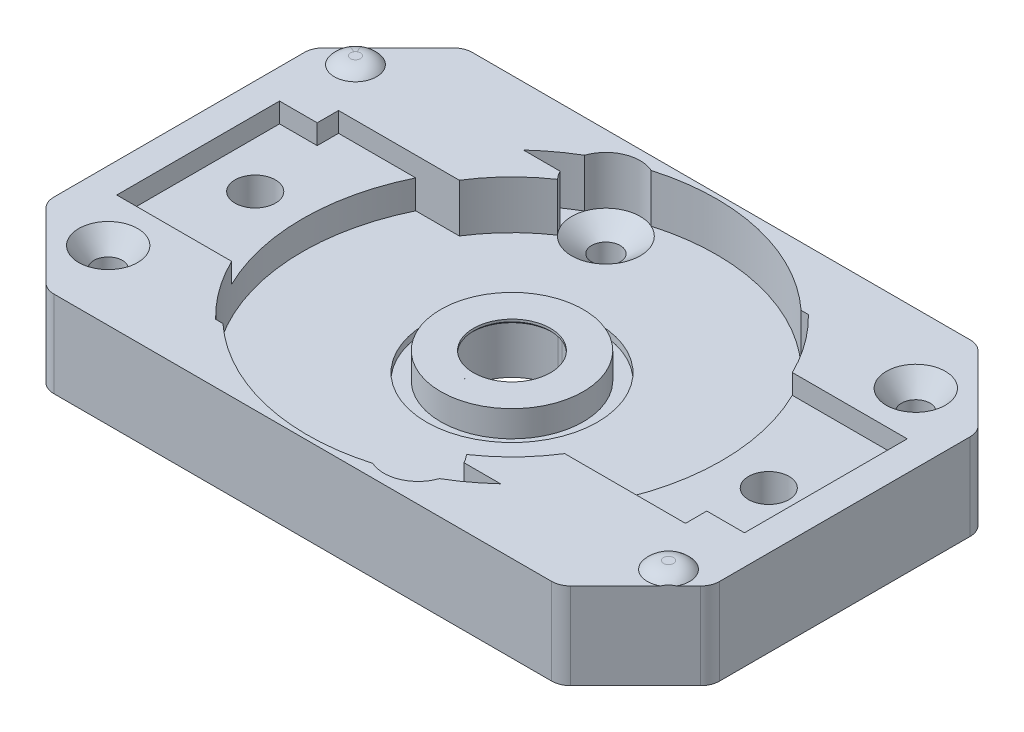
SolidWorks part; units mm, degrees
ref_plane "Front Plane" through (0, 0, 0) normal (0, 0, 1) x (1, 0, 0)
ref_plane "Top Plane" through (0, 0, 0) normal (0, 1, 0) x (1, 0, 0)
ref_plane "Right Plane" through (0, 0, 0) normal (1, 0, 0) x (0, 0, -1)
sketch "Sketch3" plane through (0, 0, 0) normal (0, 1, 0) x (-1, 0, 0)
  line L53 (-27.5858, 21.4142) -> (-34.4142, 14.5858)
  line L55 (-35, 13.1716) -> (-35, -13.1716)
  line L56 (-34.4142, -14.5858) -> (-27.5858, -21.4142)
  line L57 (-26.1716, -22) -> (26.1716, -22)
  line L58 (27.5858, -21.4142) -> (34.4142, -14.5858)
  line L59 (35, -13.1716) -> (35, 13.1716)
  line L60 (34.4142, 14.5858) -> (27.5858, 21.4142)
  line L61 (26.1716, 22) -> (-26.1716, 22)
  line L62 (21.5631, 19) -> (-21.5631, 19)
  line L63 (32, 12.7574) -> (28.5281, 16.2292)
  line L64 (32, -12.7574) -> (32, 12.7574)
  line L65 (28.5281, -16.2292) -> (32, -12.7574)
  line L67 (-21.5631, -19) -> (21.5631, -19)
  line L68 (-32, -12.7574) -> (-28.5281, -16.2292)
  line L69 (-32, 12.7574) -> (-32, -12.7574)
  line L70 (-28.5281, 16.2292) -> (-32, 12.7574)
  line L71 (0, 22) -> (0, -22) construction
  line L73 (-35, 0) -> (35, 0) construction
  circle A2 centre (0, -3.937) radius 1.125
  circle A4 centre (0, 3.937) radius 1.125
  circle A6 centre (25, -17.5) radius 1.5
  arc A7 (-34.4142, 14.5858) -> (-35, 13.1716) centre (-33, 13.1716) ccw
  circle A8 centre (0, 0) radius 7.493
  arc A10 (-35, -13.1716) -> (-34.4142, -14.5858) centre (-33, -13.1716) ccw
  circle A18 centre (0, 0) radius 1.125
  arc A19 (-27.5858, -21.4142) -> (-26.1716, -22) centre (-26.1716, -20) ccw
  arc A47 (26.1716, -22) -> (27.5858, -21.4142) centre (26.1716, -20) ccw
  arc A48 (34.4142, -14.5858) -> (35, -13.1716) centre (33, -13.1716) ccw
  arc A49 (35, 13.1716) -> (34.4142, 14.5858) centre (33, 13.1716) ccw
  arc A50 (27.5858, 21.4142) -> (26.1716, 22) centre (26.1716, 20) ccw
  arc A51 (-26.1716, 22) -> (-27.5858, 21.4142) centre (-26.1716, 20) ccw
  arc A52 (-28.5281, 16.2292) -> (-21.5631, 19) centre (-25, 17.5) ccw
  arc A53 (21.5631, 19) -> (28.5281, 16.2292) centre (25, 17.5) ccw
  arc A54 (28.5281, -16.2292) -> (21.5631, -19) centre (25, -17.5) ccw
  arc A55 (-21.5631, -19) -> (-28.5281, -16.2292) centre (-25, -17.5) ccw
  circle A56 centre (25, 17.5) radius 1.5
  circle A57 centre (-25, 17.5) radius 1.5
  circle A58 centre (-25, -17.5) radius 1.5
  point P0 (0, 0)
  dimension "D1" = 14.986
  dimension "D2" = 2.25
  dimension "D5" = 3
  dimension "D3" = 7.874
extrude "Boss-Extrude1" add sketch "Sketch3" along normal blind 4 contours A8 | A8 A18 A2 A4 | L61 A51 L53 A7 L55 A10 L56 A19 L57 A47 L58 A48 L59 A49 L60 A50 A58 A57 A56 A6 L67 A55 L68 L69 L70 A52 L62 A53 L63 L64 L65 A54 | A58 | A6 | A56 | A57 region at (26.6205, 0, 21.0839) region at (-23.3387, 0, 13.324) region at (-25, 0, -17.5) region at (7.2811, 0, 0) region at (-25, 0, 17.5) region at (25, 0, 17.5) region at (25, 0, -17.5)
sketch "Sketch2" plane through (0, 4, 0) normal (0, 1, 0) x (1, 0, 0)
  line L0 (8.6989, -15.799) -> (22.987, -15.799)
  line L2 (-27.9195, 7.436) -> (-27.9195, 9.678)
  line L3 (-27.9195, 9.678) -> (-15.2189, 9.678)
  line L4 (27.9195, -9.678) -> (27.9195, -7.436)
  line L5 (15.2189, -9.678) -> (27.9195, -9.678)
  line L7 (-22.987, -15.799) -> (-15.3666, -15.799)
  line L9 (-22.987, 15.799) -> (-8.6989, 15.799)
  line L11 (15.3666, 15.799) -> (22.987, 15.799)
  line L12 (-31.8805, -9.678) -> (-19.8009, -9.678)
  line L13 (-31.8805, -9.678) -> (-31.8805, 7.436)
  line L14 (-31.8805, 7.436) -> (-27.9195, 7.436)
  line L15 (31.8805, 9.678) -> (19.8009, 9.678)
  line L16 (31.8805, 9.678) -> (31.8805, -7.436)
  line L17 (31.8805, -7.436) -> (27.9195, -7.436)
  line L19 (-22.987, -15.799) -> (-22.987, -22)
  line L21 (22.987, -15.799) -> (22.987, -22)
  line L25 (-31.8805, 0) -> (31.8805, 0) construction
  line L26 (22.987, 15.799) -> (22.987, 22)
  line L28 (-22.987, 15.799) -> (-22.987, 22)
  line L33 (-26.1716, -22) -> (26.1716, -22)
  line L34 (27.5858, -21.4142) -> (34.4142, -14.5858)
  line L35 (35, -13.1716) -> (35, 13.1716)
  line L36 (34.4142, 14.5858) -> (27.5858, 21.4142)
  line L37 (26.1716, 22) -> (-26.1716, 22)
  line L38 (-27.5858, 21.4142) -> (-34.4142, 14.5858)
  line L40 (-35, 13.1716) -> (-35, -13.1716)
  line L41 (-34.4142, -14.5858) -> (-27.5858, -21.4142)
  line L42 (-26.1716, -22) -> (26.1716, -22)
  line L43 (27.5858, -21.4142) -> (34.4142, -14.5858)
  line L44 (35, -13.1716) -> (35, 13.1716)
  line L46 (34.4142, 14.5858) -> (27.5858, 21.4142)
  line L48 (26.1716, 22) -> (-26.1716, 22)
  line L49 (-27.5858, 21.4142) -> (-34.4142, 14.5858)
  line L51 (-35, 13.1716) -> (-35, -13.1716)
  line L53 (-34.4142, -14.5858) -> (-27.5858, -21.4142)
  arc A0 (-19.8009, -9.678) -> (-15.3666, -15.799) centre (0, 0) ccw
  arc A1 (8.6989, -15.799) -> (15.2189, -9.678) centre (0, 0) ccw
  arc A2 (-8.6989, 15.799) -> (-15.2189, 9.678) centre (0, 0) ccw
  arc A3 (19.8009, 9.678) -> (15.3666, 15.799) centre (0, 0) ccw
  circle A4 centre (-27, 0) radius 2.125
  circle A5 centre (27, 0) radius 2.125
  arc A6 (-19.8009, -9.678) -> (-19.8009, 9.678) centre (0, 0) cw
  arc A7 (19.8009, 9.678) -> (19.8009, -9.678) centre (0, 0) cw
  arc A22 (26.1716, -22) -> (27.5858, -21.4142) centre (26.1716, -20) ccw
  arc A24 (34.4142, -14.5858) -> (35, -13.1716) centre (33, -13.1716) ccw
  arc A25 (35, 13.1716) -> (34.4142, 14.5858) centre (33, 13.1716) ccw
  arc A27 (27.5858, 21.4142) -> (26.1716, 22) centre (26.1716, 20) ccw
  arc A28 (-26.1716, 22) -> (-27.5858, 21.4142) centre (-26.1716, 20) ccw
  arc A42 (-34.4142, 14.5858) -> (-35, 13.1716) centre (-33, 13.1716) ccw
  arc A43 (-35, -13.1716) -> (-34.4142, -14.5858) centre (-33, -13.1716) ccw
  arc A56 (-27.5858, -21.4142) -> (-26.1716, -22) centre (-26.1716, -20) ccw
  arc A57 (26.1716, -22) -> (27.5858, -21.4142) centre (26.1716, -20) ccw
  arc A58 (34.4142, -14.5858) -> (35, -13.1716) centre (33, -13.1716) ccw
  arc A59 (35, 13.1716) -> (34.4142, 14.5858) centre (33, 13.1716) ccw
  arc A60 (27.5858, 21.4142) -> (26.1716, 22) centre (26.1716, 20) ccw
  arc A61 (-26.1716, 22) -> (-27.5858, 21.4142) centre (-26.1716, 20) ccw
  arc A62 (-34.4142, 14.5858) -> (-35, 13.1716) centre (-33, 13.1716) ccw
  arc A63 (-35, -13.1716) -> (-34.4142, -14.5858) centre (-33, -13.1716) ccw
  arc A64 (-27.5858, -21.4142) -> (-26.1716, -22) centre (-26.1716, -20) ccw
  dimension "D1" = 36.071
  dimension "D2" = 44.079
  dimension "D8" = 4.25
  dimension "D3" = 55.839
  dimension "D4" = 63.761
  dimension "D5" = 19.356
  dimension "D6" = 31.598
  dimension "D7" = 54
  dimension "D9" = 2.242
  dimension "D10" = 2.242
  dimension "D11" = 0
extrude "Boss-Extrude2" add sketch "Sketch2" along normal blind 3 contours L15 A7 L5 L4 L17 L16 A5 | L12 A6 L3 L2 L14 L13 A4 | L25 L13 L12 A6 A4 | A7 L25 A5 L16 L15 region at (26.197, 4, 4.9802) region at (26.5424, 4, -5.3138) region at (-26.5424, 4, 5.3138) region at (-26.197, 4, -4.9802)
extrude "Boss-Extrude3" add sketch "Sketch2<4>" along normal blind 5.08 contours A3 L15 L16 L17 L4 L5 A1 L0 L11 | A2 L9 L7 A0 L12 L13 L14 L2 L3 region at (12.6952, 4, 13.5228) region at (-24.5793, 4, 21.4874)
sketch "Sketch2<4>" plane through (0, 4, 0) normal (0, 1, 0) x (1, 0, 0) same geometry as "Sketch2"
sketch "Sketch4" plane through (0, 4, 0) normal (0, 1, 0) x (1, 0, 0)
  circle A0 centre (0, 0) radius 7.493
  circle A1 centre (0, 0) radius 9
  circle A2 centre (0, 3.937) radius 1.125
  circle A3 centre (0, 0) radius 1.125
  circle A4 centre (0, -3.937) radius 1.125
  dimension "D1" = 14.986
  dimension "D2" = 18
extrude "Boss-Extrude4" add sketch "Sketch4" along normal blind 2.02 contours A0 A4 A3 A2 region at (-7.2811, 4, 0)
extrude "Cut-Extrude1" cut sketch "Sketch4<3>" against normal blind 0.728 contours A1 A0 region at (-8.7454, 4, 0)
sketch "Sketch4<3>" plane through (0, 4, 0) normal (0, 1, 0) x (1, 0, 0) same geometry as "Sketch4"
sketch "Sketch7" plane through (0, 7, 0) normal (0, 1, 0) x (1, 0, 0)
  circle A0 centre (-27, 0) radius 2.125
  circle A1 centre (27, 0) radius 2.125
extrude "Cut-Extrude3" cut sketch "Sketch7" against normal through all
sketch "Sketch8" plane through (0, 0, 0) normal (0, -1, 0) x (1, 0, 0)
  circle A0 centre (-27.7296, 14.7296) radius 1.5
  circle A1 centre (7.5, 17.375) radius 1.5
  circle A2 centre (27.7296, -14.7296) radius 1.5
  circle A3 centre (-7.5, -17.375) radius 1.5
  dimension "D1" = 3
extrude "Cut-Extrude4" cut sketch "Sketch8" against normal through all
sketch "Sketch10" plane through (0, 4, 0) normal (0, 1, 0) x (1, 0, 0)
  circle A0 centre (7.5, -17.375) radius 3.6
  circle A1 centre (-7.5, 17.375) radius 3.6
  dimension "D1" = 7.2
extrude "Cut-Extrude6" cut sketch "Sketch10" along normal through all
chamfer "Chamfer1" distance 2.1 distance2 1.6 4 edges at (-27.7296, 9.08, 13.2296) (-7.5, 4, -15.875) (7.5, 4, 18.875) (27.7296, 9.08, -16.2296) first distance on face at (-27.7296, 9.08, 13.2296) first distance on face at (0, 4, 9) first distance on face at (27.7296, 9.08, -16.2296)
sketch "Sketch11" plane through (0, 9.08, 0) normal (0, 1, 0) x (1, 0, 0)
  line L0 (0, 0) -> (0, -22) construction
  line L1 (31.2095, -14.7515) -> (-31.2095, -14.7515)
  line L2 (31.2095, -14.7515) -> (31.2095, 14.7515)
  line L3 (31.2095, 14.7515) -> (-31.2095, 14.7515)
  line L4 (-31.2095, -14.7515) -> (-31.2095, 14.7515)
  line L5 (-22.987, -22) -> (22.987, -22) construction
  circle A0 centre (31.2095, -14.7515) radius 2.2255
  circle A1 centre (-31.2095, 14.7515) radius 2.2255
  point P11 (-31.2095, 0)
  point P12 (0, -14.7515)
  line M11 (27.5858, -21.4142) -> (34.4142, -14.5858)
  dimension "D1" = 4.451
  dimension "D2" = 29.503
  dimension "D3" = 62.419
extrude "Boss-Extrude5" add sketch "Sketch11" along normal blind 0.8 contours L3 A1 L4 | L4 A1 L3 | L2 A0 L1 | A0 L2 L1 M11 region at (31.5181, 9.08, 15.0601) region at (30.265, 9.08, 13.807) region at (-31.5243, 9.08, -15.0663) region at (-30.265, 9.08, -13.807)
fillet "Fillet1" radius 2.2 2 edges at (-31.2095, 9.88, -12.526) (29.6358, 9.88, 13.1778)
sketch "Sketch12" plane through (0, 4, 0) normal (0, 1, 0) x (1, 0, 0)
  line L0 (-22.987, -15.799) -> (-14.6001, -15.799)
  line L1 (-22.987, -15.799) -> (-22.987, -22)
  line L2 (-22.987, -22) -> (22.987, -22)
  line L3 (22.987, -22) -> (22.987, -15.799)
  line L4 (22.987, -15.799) -> (14.6001, -15.799)
  line L5 (10.7367, -15.799) -> (22.987, -15.799) construction
  line L6 (-21.5121, 0) -> (21.5121, 0) construction
  line L7 (22.987, 15.799) -> (14.6001, 15.799)
  line L8 (22.987, 22) -> (22.987, 15.799)
  line L9 (-22.987, 15.799) -> (-22.987, 22)
  line L10 (-22.987, 22) -> (22.987, 22)
  line L11 (-22.987, 15.799) -> (-14.6001, 15.799)
  circle A0 centre (0, 0) radius 21.5121
  line M2 (-22.987, 15.799) -> (-10.7367, 15.799)
  arc M3 (-10.7367, 15.799) -> (-10.1329, 14.9199) centre (-7.5, 17.375) cw
  line M7 (-15.3666, -15.799) -> (-22.987, -15.799)
  line M8 (-22.987, -15.799) -> (-22.987, -22)
  line M9 (-22.987, -22) -> (22.987, -22)
  line M10 (22.987, -22) -> (22.987, -15.799)
  line M11 (22.987, -15.799) -> (10.7367, -15.799)
  arc M12 (10.7367, -15.799) -> (10.1329, -14.9199) centre (7.5, -17.375) cw
  line M16 (15.3666, 15.799) -> (22.987, 15.799)
  line M17 (22.987, 15.799) -> (22.987, 22)
  line M18 (22.987, 22) -> (-22.987, 22)
  line M19 (-22.987, 22) -> (-22.987, 15.799)
  dimension "D1" = 43.0242
extrude "Boss-Extrude6" add sketch "Sketch12" along normal up to surface (5.08 mm away) contours A0 L0 M12 M7 M8 M9 M10 M11 | A0 L7 M16 M17 M18 M19 M2 M3 region at (-19.1768, 4, 16.2629) region at (-18.7935, 4, -16.2629) up to face at (-27.7296, 9.08, 17.8296)
sketch "Sketch13" plane through (0, 6.02, 0) normal (0, 1, 0) x (1, 0, 0)
  circle A0 centre (0, 0) radius 5.05
  dimension "D1" = 10.1
extrude "Cut-Extrude7" cut sketch "Sketch13" against normal through all
sketch "Sketch14" plane through (0, 6.02, 0) normal (0, 1, 0) x (1, 0, 0)
  circle A0 centre (0, 0) radius 5.05
  circle A1 centre (0, 0) radius 4.05
  arc A2 (-0.1856, 5.0466) -> (-0.1856, -5.0466) centre (0, 0) ccw construction
  dimension "D1" = 8.1
extrude "Boss-Extrude7" add sketch "Sketch14" against normal blind 0.5
chamfer "Chamfer2" distance 0.25 angle 45 1 edges at (0, 5.52, 4.05)
